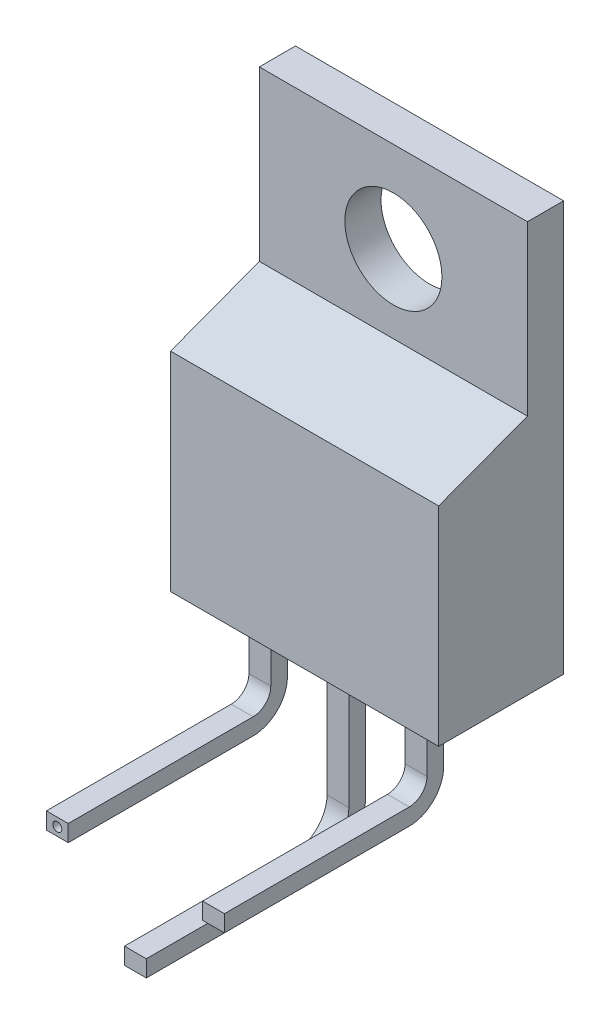
SolidWorks part; units mm, degrees
ref_plane "Front" through (0, 0, 0) normal (0, 0, 1) x (1, 0, 0)
ref_plane "Top" through (0, 0, 0) normal (0, 1, 0) x (1, 0, 0)
ref_plane "Right" through (0, 0, 0) normal (1, 0, 0) x (0, 0, -1)
sketch "Эскиз1" plane through (0, 0, 0) normal (0, 0, 1) x (1, 0, 0)
  line L1 (-1, -1) -> (1, -1)
  line L2 (-1, -1) -> (-1, 1)
  line L3 (-1, 1) -> (1, 1)
  line L4 (1, -1) -> (1, 1)
  line L5 (4.08, -1) -> (6.08, -1)
  line L6 (4.08, -1) -> (4.08, 1)
  line L7 (4.08, 1) -> (6.08, 1)
  line L8 (6.08, -1) -> (6.08, 1)
  line L9 (1.54, -2.5) -> (3.54, -2.5)
  line L10 (1.54, -2.5) -> (1.54, -0.5)
  line L11 (1.54, -0.5) -> (3.54, -0.5)
  line L12 (3.54, -2.5) -> (3.54, -0.5)
sketch "Эскиз3" plane through (0, 0, 0) normal (0, 0, 1) x (1, 0, 0)
  line L0 (-0.42, 0) -> (0.42, 0) construction
  line L1 (-0.42, 0.32) -> (0.42, 0.32)
  line L2 (-0.42, 0.32) -> (-0.42, -0.32)
  line L3 (-0.42, -0.32) -> (0.42, -0.32)
  line L4 (0.42, 0.32) -> (0.42, -0.32)
  line L5 (0, 0.32) -> (0, -0.32) construction
  line L6 (2.54, 1.6352) -> (2.54, -3.5178) construction
  line L8 (4.66, 0.32) -> (4.66, -0.32)
  line L9 (5.5, -0.32) -> (4.66, -0.32)
  line L10 (5.5, 0.32) -> (4.66, 0.32)
  line L11 (5.5, 0.32) -> (5.5, -0.32)
  dimension "D1" = 0.84
  dimension "D2" = 0.64
  dimension "D3" = 2.54
sketch "Эскиз4" plane through (0, 0, 0) normal (0, 0, 1) x (1, 0, 0)
  line L0 (2.12, -2.54) -> (2.96, -2.54) construction
  line L1 (2.12, -2.22) -> (2.96, -2.22)
  line L2 (2.12, -2.22) -> (2.12, -2.86)
  line L3 (2.12, -2.86) -> (2.96, -2.86)
  line L4 (2.96, -2.22) -> (2.96, -2.86)
  line L5 (2.54, -2.22) -> (2.54, -2.86) construction
  point P8 (2.54, -2.54)
  dimension "D1" = 0.84
  dimension "D2" = 0.64
  dimension "D3" = 2.54
  dimension "D4" = 2.54
ref_plane "Плоскость1" through (0, 3.5, 0) normal (0, 1, 0) x (-1, 0, 0)
sketch "Эскиз5" plane through (0, 3.5, 0) normal (0, 1, 0) x (-1, 0, 0)
  line L0 (-2.54, 0) -> (-2.54, -4.8) construction
  line L1 (2.61, 0) -> (-7.69, 0)
  line L3 (-7.69, 0) -> (-7.69, -4.8)
  line L5 (-9.4262, 0) -> (-8.0568, 0) construction
  line L6 (2.61, -4.8) -> (-7.69, -4.8)
  line L7 (2.61, 0) -> (2.61, -4.8)
  dimension "D1" = 4.8
  dimension "D2" = 10.3
  dimension "D3" = 2.54
sketch "Эскиз8" plane through (0, 0, 0) normal (1, 0, 0) x (0, 0, -1)
  line L1 (0, 0) -> (0.6, 0)
  line L3 (0, 3.1835) -> (0, 2.5724) construction
  line L4 (1.6, 1) -> (1.6, 3.5)
  arc A1 (0.6, 0) -> (1.6, 1) centre (0.6, 1) ccw
  point P12 (0, 0)
  dimension "D2" = 1.6
  dimension "D1" = 1
  dimension "D4" = 3.5
  dimension "D5" = 0.6
  dimension "D6" = 2.5
sketch "Эскиз9" plane through (0, 0, 0) normal (1, 0, 0) x (0, 0, -1)
  line L1 (0, -2.54) -> (0.6, -2.54)
  line L2 (0, -1.6929) -> (0, -2.6032) construction
  line L3 (0, 1.6352) -> (0, -3.5178) construction
  line L4 (1.6, -1.54) -> (1.6, 4.77)
  arc A1 (0.6, -2.54) -> (1.6, -1.54) centre (0.6, -1.54) ccw
  point P14 (0, -2.54)
  dimension "D2" = 1.6
  dimension "D4" = 0.6
  dimension "D3" = 1
  dimension "D1" = 2.54
  dimension "D5" = 6.31
  dimension "D6" = 7.31
extrude "Вытянуть1" add sketch "Эскиз5" along normal blind 15.75
sketch "Эскиз10" plane through (0, 0, 0) normal (1, 0, 0) x (0, 0, -1)
  line L0 (0, 19.25) -> (3.41, 19.25)
  line L2 (3.41, 19.25) -> (3.41, 12.78)
  line L3 (3.41, 12.78) -> (0, 11.5)
  line L5 (0, 11.5) -> (0, 19.25)
  dimension "D1" = 6.47
  dimension "D2" = 3.41
  dimension "D3" = 7.75
extrude "Вырез-Вытянуть1" cut sketch "Эскиз10" against normal up to surface and the other way up to surface up to face at (-2.61, 11.375, -2.4) other way up to face at (7.69, 11.375, -2.4)
sketch "Эскиз11" plane through (0, 0, 0) normal (0, 0, 1) x (1, 0, 0)
  circle A0 centre (2.54, 15.77) radius 1.865
  dimension "D3" = 3.73
extrude "Вырез-Вытянуть2" cut sketch "Эскиз11" against normal up to surface (4.8 mm away) up to face at (2.54, 11.375, -4.8)
sweep "По траектории1" add profiles "Эскиз3" path "Эскиз8"
sweep "По траектории2" add profiles "Эскиз4" path "Эскиз9"
extrude "Вытянуть2" add sketch "Эскиз3<3>" along normal blind 2.5
sketch "Эскиз3<3>" plane through (0, 0, 0) normal (0, 0, 1) x (1, 0, 0) same geometry as "Эскиз3"
extrude "Вытянуть3" add sketch "Эскиз4<3>" along normal blind 2.5
sketch "Эскиз4<3>" plane through (0, 0, 0) normal (0, 0, 1) x (1, 0, 0) same geometry as "Эскиз4"
sketch "Эскиз12" plane through (0, 0, 2.5) normal (0, 0, 1) x (1, 0, 0)
  line L4 (-0.42, 0.32) -> (-0.42, -0.32)
  line L5 (-0.42, -0.32) -> (0.42, -0.32)
  line L6 (0.42, -0.32) -> (0.42, 0.32)
  line L7 (0.42, 0.32) -> (-0.42, 0.32)
  line L8 (-0.42, 0.32) -> (-0.42, -0.32)
  line L9 (-0.42, -0.32) -> (0.42, -0.32)
  line L10 (0.42, -0.32) -> (0.42, 0.32)
  line L11 (0.42, 0.32) -> (-0.42, 0.32)
  line L12 (5.5, 0.32) -> (4.66, 0.32)
  line L13 (4.66, 0.32) -> (4.66, -0.32)
  line L14 (4.66, -0.32) -> (5.5, -0.32)
  line L15 (5.5, -0.32) -> (5.5, 0.32)
  line L16 (5.5, 0.32) -> (4.66, 0.32)
  line L17 (4.66, 0.32) -> (4.66, -0.32)
  line L18 (4.66, -0.32) -> (5.5, -0.32)
  line L19 (5.5, -0.32) -> (5.5, 0.32)
  line L20 (2.12, -2.22) -> (2.12, -2.86)
  line L21 (2.12, -2.86) -> (2.96, -2.86)
  line L22 (2.96, -2.86) -> (2.96, -2.22)
  line L23 (2.96, -2.22) -> (2.12, -2.22)
  line L24 (2.12, -2.22) -> (2.12, -2.86)
  line L25 (2.12, -2.86) -> (2.96, -2.86)
  line L26 (2.96, -2.86) -> (2.96, -2.22)
  line L27 (2.96, -2.22) -> (2.12, -2.22)
  dimension "D1" = 0
  dimension "D2" = 0
  dimension "D3" = 0
extrude "Вытянуть4" add sketch "Эскиз12" along normal blind 4
sketch "Эскиз13" plane through (-0.42, 0, 0) normal (-1, 0, 0) x (0, 0, 1)
  line L6 (-0.6, -0.32) -> (6.5, -0.32)
  line L7 (6.5, -0.32) -> (6.5, 0.32)
  line L8 (6.5, 0.32) -> (-0.6, 0.32)
  line L9 (-1.28, 1) -> (-1.28, 3.5)
  line L10 (-1.28, 3.5) -> (-1.92, 3.5)
  line L11 (-1.92, 3.5) -> (-1.92, 1)
  line L12 (-0.6, -0.32) -> (6.5, -0.32)
  line L13 (6.5, -0.32) -> (6.5, 0.32)
  line L14 (6.5, 0.32) -> (-0.6, 0.32)
  line L15 (-1.28, 1) -> (-1.28, 3.5)
  line L16 (-1.28, 3.5) -> (-1.92, 3.5)
  line L17 (-1.92, 3.5) -> (-1.92, 1)
  arc A2 (-1.28, 1) -> (-0.6, 0.32) centre (-0.6, 1) ccw
  arc A3 (-1.92, 1) -> (-0.6, -0.32) centre (-0.6, 1) ccw
  arc A4 (-1.28, 1) -> (-0.6, 0.32) centre (-0.6, 1) ccw
  arc A5 (-1.92, 1) -> (-0.6, -0.32) centre (-0.6, 1) ccw
  dimension "D1" = 0
extrude "Вытянуть5" add sketch "Эскиз13" along normal blind 0.46
sketch "Эскиз14" plane through (5.5, 0, 0) normal (1, 0, 0) x (0, 0, -1)
  line L6 (0.6, 0.32) -> (-6.5, 0.32)
  line L7 (-6.5, 0.32) -> (-6.5, -0.32)
  line L8 (-6.5, -0.32) -> (0.6, -0.32)
  line L9 (1.92, 1) -> (1.92, 3.5)
  line L10 (1.92, 3.5) -> (1.28, 3.5)
  line L11 (1.28, 3.5) -> (1.28, 1)
  line L12 (0.6, 0.32) -> (-6.5, 0.32)
  line L13 (-6.5, 0.32) -> (-6.5, -0.32)
  line L14 (-6.5, -0.32) -> (0.6, -0.32)
  line L15 (1.92, 1) -> (1.92, 3.5)
  line L16 (1.92, 3.5) -> (1.28, 3.5)
  line L17 (1.28, 3.5) -> (1.28, 1)
  arc A2 (0.6, -0.32) -> (1.92, 1) centre (0.6, 1) ccw
  arc A3 (0.6, 0.32) -> (1.28, 1) centre (0.6, 1) ccw
  arc A4 (0.6, -0.32) -> (1.92, 1) centre (0.6, 1) ccw
  arc A5 (0.6, 0.32) -> (1.28, 1) centre (0.6, 1) ccw
  dimension "D1" = 0
extrude "Вытянуть6" add sketch "Эскиз14" along normal blind 0.46
sketch "Эскиз15" plane through (4.66, 0, 0) normal (-1, 0, 0) x (0, 0, 1)
  line L6 (-0.6, -0.32) -> (6.5, -0.32)
  line L7 (6.5, -0.32) -> (6.5, 0.32)
  line L8 (6.5, 0.32) -> (-0.6, 0.32)
  line L9 (-1.28, 1) -> (-1.28, 3.5)
  line L10 (-1.28, 3.5) -> (-1.92, 3.5)
  line L11 (-1.92, 3.5) -> (-1.92, 1)
  line L12 (-0.6, -0.32) -> (6.5, -0.32)
  line L13 (6.5, -0.32) -> (6.5, 0.32)
  line L14 (6.5, 0.32) -> (-0.6, 0.32)
  line L15 (-1.28, 1) -> (-1.28, 3.5)
  line L16 (-1.28, 3.5) -> (-1.92, 3.5)
  line L17 (-1.92, 3.5) -> (-1.92, 1)
  arc A2 (-1.28, 1) -> (-0.6, 0.32) centre (-0.6, 1) ccw
  arc A3 (-1.92, 1) -> (-0.6, -0.32) centre (-0.6, 1) ccw
  arc A4 (-1.28, 1) -> (-0.6, 0.32) centre (-0.6, 1) ccw
  arc A5 (-1.92, 1) -> (-0.6, -0.32) centre (-0.6, 1) ccw
  dimension "D1" = 0
extrude "Вырез-Вытянуть3" cut sketch "Эскиз15" against normal blind 0.46
sketch "Эскиз16" plane through (0.42, 0, 0) normal (1, 0, 0) x (0, 0, -1)
  line L6 (0.6, 0.32) -> (-6.5, 0.32)
  line L7 (-6.5, 0.32) -> (-6.5, -0.32)
  line L8 (-6.5, -0.32) -> (0.6, -0.32)
  line L9 (1.92, 1) -> (1.92, 3.5)
  line L10 (1.92, 3.5) -> (1.28, 3.5)
  line L11 (1.28, 3.5) -> (1.28, 1)
  line L12 (0.6, 0.32) -> (-6.5, 0.32)
  line L13 (-6.5, 0.32) -> (-6.5, -0.32)
  line L14 (-6.5, -0.32) -> (0.6, -0.32)
  line L15 (1.92, 1) -> (1.92, 3.5)
  line L16 (1.92, 3.5) -> (1.28, 3.5)
  line L17 (1.28, 3.5) -> (1.28, 1)
  arc A2 (0.6, -0.32) -> (1.92, 1) centre (0.6, 1) ccw
  arc A3 (0.6, 0.32) -> (1.28, 1) centre (0.6, 1) ccw
  arc A4 (0.6, -0.32) -> (1.92, 1) centre (0.6, 1) ccw
  arc A5 (0.6, 0.32) -> (1.28, 1) centre (0.6, 1) ccw
  dimension "D1" = 0
extrude "Вырез-Вытянуть4" cut sketch "Эскиз16" against normal blind 0.46
sketch "Эскиз17" plane through (0, 0, 6.5) normal (0, 0, 1) x (1, 0, 0)
  line L0 (-0.46, 0.5203) -> (-0.46, -0.5717) construction
  line L1 (-1.074, 0) -> (0.331, 0) construction
  line L2 (-0.04, 0.32) -> (-0.88, 0.32) construction
  line L3 (-0.88, -0.32) -> (-0.04, -0.32) construction
  line L4 (-0.04, 0.32) -> (-0.04, -0.32) construction
  line L5 (-0.88, -0.32) -> (-0.88, 0.32) construction
  circle A0 centre (-0.46, 0) radius 0.173
extrude "Вырез-Вытянуть5" cut sketch "Эскиз17" against normal blind 2
sketch "Эскиз18" plane through (2.12, 0, 0) normal (-1, 0, 0) x (0, 0, 1)
  line L1 (-3.9602, -4.9109) -> (7.9707, -4.9109)
  line L2 (-3.9602, -4.9109) -> (-3.9602, -1.54)
  line L3 (-3.9602, -1.54) -> (7.9707, -1.54)
  line L4 (7.9707, -4.9109) -> (7.9707, -1.54)
extrude "Вырез-Вытянуть6" cut sketch "Эскиз18" against normal blind 2
sketch "Эскиз19" plane through (2.12, 0, 0) normal (-1, 0, 0) x (0, 0, 1)
  line L2 (-3.5264, -1.2296) -> (7.0018, -1.2296) construction
  line L6 (6.5, -0.32) -> (6.5, 0.32) construction
  line L7 (-0.6, -3.32) -> (6.5, -3.32)
  line L9 (-0.6, -2.68) -> (6.5, -2.68)
  line L10 (6.5, -3.32) -> (6.5, -2.68)
  line L11 (-0.6, -0.32) -> (6.5, -0.32) construction
  line L12 (6.5, 0.32) -> (-0.6, 0.32) construction
  line L13 (-1.28, -1.54) -> (-1.92, -1.54) construction
  line L14 (-1.28, -1.54) -> (-1.92, -1.54)
  arc A4 (-1.92, -1.54) -> (-0.6, -3.32) centre (-0.0598, -1.54) ccw
  arc A5 (-1.28, -1.54) -> (-0.6, -2.68) centre (0.0156, -1.54) ccw
  dimension "D1" = 3
extrude "Вытянуть7" add sketch "Эскиз19" against normal up to surface (0.84 mm away)
